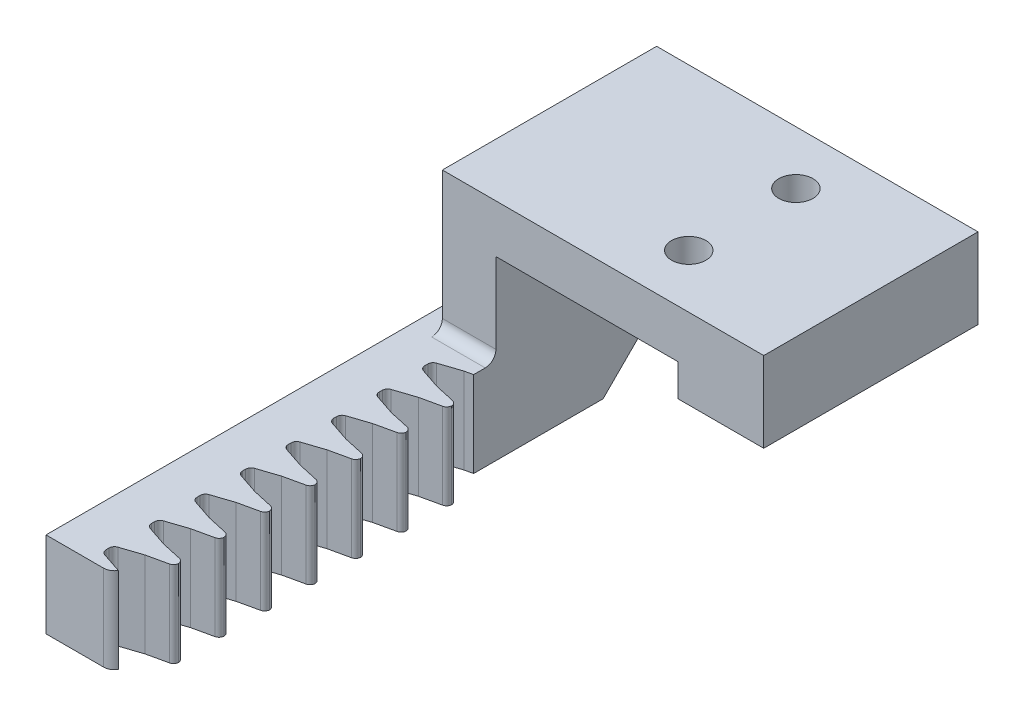
SolidWorks part; units mm, degrees
ref_plane "Front Plane" through (0, 0, 0) normal (0, 0, 1) x (1, 0, 0)
ref_plane "Top Plane" through (0, 0, 0) normal (0, 1, 0) x (1, 0, 0)
ref_plane "Right Plane" through (0, 0, 0) normal (1, 0, 0) x (0, 0, -1)
sketch "Sketch1" plane through (0, 0, 0) normal (0, 0, 1) x (1, 0, 0)
  line L1 (0, 0) -> (30, 0)
  line L2 (0, 0) -> (0, -16)
  line L3 (0, -16) -> (30, -16)
  line L4 (30, 0) -> (30, -16)
  dimension "D1" = 30
  dimension "D2" = 16
extrude "Boss-Extrude1" add sketch "Sketch1" along normal blind 20
sketch "Sketch2" plane through (0, 0, 20) normal (0, 0, 1) x (1, 0, 0)
  line L0 (22, -4.5) -> (22, -7.5)
  line L7 (5, -16) -> (5, -4.5)
  line L8 (5, -4.5) -> (22, -4.5)
  line L14 (22, -7.5) -> (30, -7.5)
  line L15 (30, -16) -> (30, 0) construction
  line L16 (30, -7.5) -> (30, -16)
  line L17 (30, -16) -> (5, -16)
  dimension "D1" = 25
  dimension "D2" = 8.5
  dimension "D3" = 3
  dimension "D7" = 17
extrude "Cut-Extrude1" cut sketch "Sketch2" against normal up to surface (20 mm away) contours L8 L0 L14 L16 L17 L7 up to face at (15, -8, 0)
sketch "Sketch3" plane through (0, -16, 0) normal (0, -1, 0) x (1, 0, 0)
  line L0 (0, 20) -> (0, 0) construction
  line L1 (0, 15) -> (6, 15)
  line L2 (0, 15) -> (0, 5)
  line L3 (0, 5) -> (6, 5)
  line L4 (6, 15) -> (6, 5)
  line L6 (0, 20) -> (5, 20) construction
  dimension "D1" = 5
  dimension "D2" = 10
  dimension "D3" = 6
extrude "Boss-Extrude2" add sketch "Sketch3" along normal blind 5
ref_plane "Plane1" through (0, 0, 0) normal (-1, 0, 0) x (0, 0, 1)
sketch "Sketch9" plane through (0, -4.5, 0) normal (0, -1, 0) x (1, 0, 0)
  line L0 (30, 0) -> (30, 20) construction
  line L3 (5, 20) -> (22, 20) construction
  circle A0 centre (18, 15) radius 1.6
  circle A1 centre (18, 5) radius 1.6
  dimension "D1" = 3.2
  dimension "D2" = 3.2
  dimension "D3" = 12
  dimension "D4" = 12
  dimension "D5" = 10
  dimension "D6" = 5
extrude "Cut-Extrude3" cut sketch "Sketch9" against normal up to surface (4.5 mm away) up to face at (15, 0, 10)
sketch "Sketch11" plane through (0, 0, 15) normal (0, 0, 1) x (1, 0, 0)
  line L0 (6, -21) -> (0, -21) construction
  line L1 (-2, -13) -> (8, -13)
  line L2 (-2, -13) -> (-2, -21)
  line L3 (-2, -21) -> (8, -21)
  line L4 (8, -13) -> (8, -21)
  line L5 (0, -21) -> (0, -16) construction
  line L6 (6, -21) -> (6, -16) construction
  dimension "D1" = 2
  dimension "D2" = 2
  dimension "D3" = 8
extrude "Boss-Extrude4" add sketch "Sketch11" along normal blind 40
chamfer "Chamfer2" distance 2 distance2 10 1 edges
fillet "Fillet1" radius 1 1 edges at (2.5, -13, 20)
sketch "Sketch12" plane through (0, -21, 0) normal (0, -1, 0) x (1, 0, 0)
  line L0 (6.5, 55) -> (4.25, 54.5)
  line L1 (4.25, 54.5) -> (2, 53.75)
  line L3 (2, 53.25) -> (8, 53.25) construction
  line L4 (8, 55) -> (8, 15) construction
  line L7 (2, 55) -> (2, 48) construction
  line L8 (-2, 55) -> (8, 55) construction
  line L14 (2, 53.75) -> (2, 52.75)
  line L15 (4.25, 52) -> (2, 52.75)
  line L16 (6.5, 51.5) -> (4.25, 52)
  line L17 (6.5, 55) -> (8, 55)
  line L18 (6.5, 51.5) -> (6.5, 50.75)
  line L19 (6.5, 50.75) -> (8, 50.75)
  line L20 (8, 50.75) -> (8, 55)
  dimension "D1" = 0.5
  dimension "D2" = 0.75
  dimension "D3" = 2.25
  dimension "D4" = 1.5
  dimension "D5" = 0.5
  dimension "D6" = 6
  dimension "D7" = 0.75
extrude "Cut-Extrude4" cut sketch "Sketch12" against normal blind 8
sketch "Sketch13" plane through (0, 0, 15) normal (0, 0, -1) x (-1, 0, 0)
  line L0 (-6, -21) -> (-8, -21) construction
  line L1 (-8, -13) -> (-6, -13)
  line L2 (-8, -13) -> (-8, -21)
  line L3 (-8, -21) -> (-6, -21)
  line L4 (-6, -13) -> (-6, -21)
extrude "Boss-Extrude5" add sketch "Sketch13" along normal blind 10
pattern_linear "LPattern1" count 8 spacing 4.25 along (0, 0, -1) of "Cut-Extrude4"
fillet "Fillet2" radius 0.5 30 edges at (2, -17, 52.75) (2, -17, 53.75) (2, -17, 48.5) (2, -17, 49.5) (2, -17, 44.25) (2, -17, 45.25) (2, -17, 35.75) (2, -17, 36.75) (2, -17, 40) (2, -17, 41) (6.5, -17, 33.75) (6.5, -17, 34.5) (6.5, -17, 38) (6.5, -17, 38.75) (6.5, -17, 42.25) (6.5, -17, 43) (6.5, -17, 46.5) (6.5, -17, 47.25) (6.5, -17, 50.75) (6.5, -17, 51.5) (6.5, -17, 25.25) (6.5, -17, 26) (6.5, -17, 29.5) (6.5, -17, 30.25) (2, -17, 23) (2, -17, 24) (2, -17, 27.25) (2, -17, 28.25) (2, -17, 32.5) (2, -17, 31.5)
fillet "Fillet3" radius 1 1 edges at (6.5, -17, 55)
sketch "Sketch14" plane through (0, 0, 5) normal (0, 0, -1) x (-1, 0, 0)
  line L1 (-6, -13) -> (-8, -13)
  line L2 (-6, -13) -> (-6, -21)
  line L3 (-6, -21) -> (-8, -21)
  line L4 (-8, -13) -> (-8, -21)
extrude "Cut-Extrude5" cut sketch "Sketch14" against normal blind 17
chamfer "Chamfer9" distance 5 angle 45 2 edges at (2.5, -16, 0)
sketch "Sketch15" plane through (6, 0, 0) normal (1, 0, 0) x (0, 0, -1)
  line L1 (-22.3938, -21) -> (-3.2737, -21)
  line L2 (-22.3938, -21) -> (-22.3938, -12.3704)
  line L3 (-22.3938, -12.3704) -> (-3.2737, -12.3704)
  line L4 (-3.2737, -21) -> (-3.2737, -12.3704)
  point P5 (0, 0)
extrude "Cut-Extrude6" cut sketch "Sketch15" against normal blind 1
